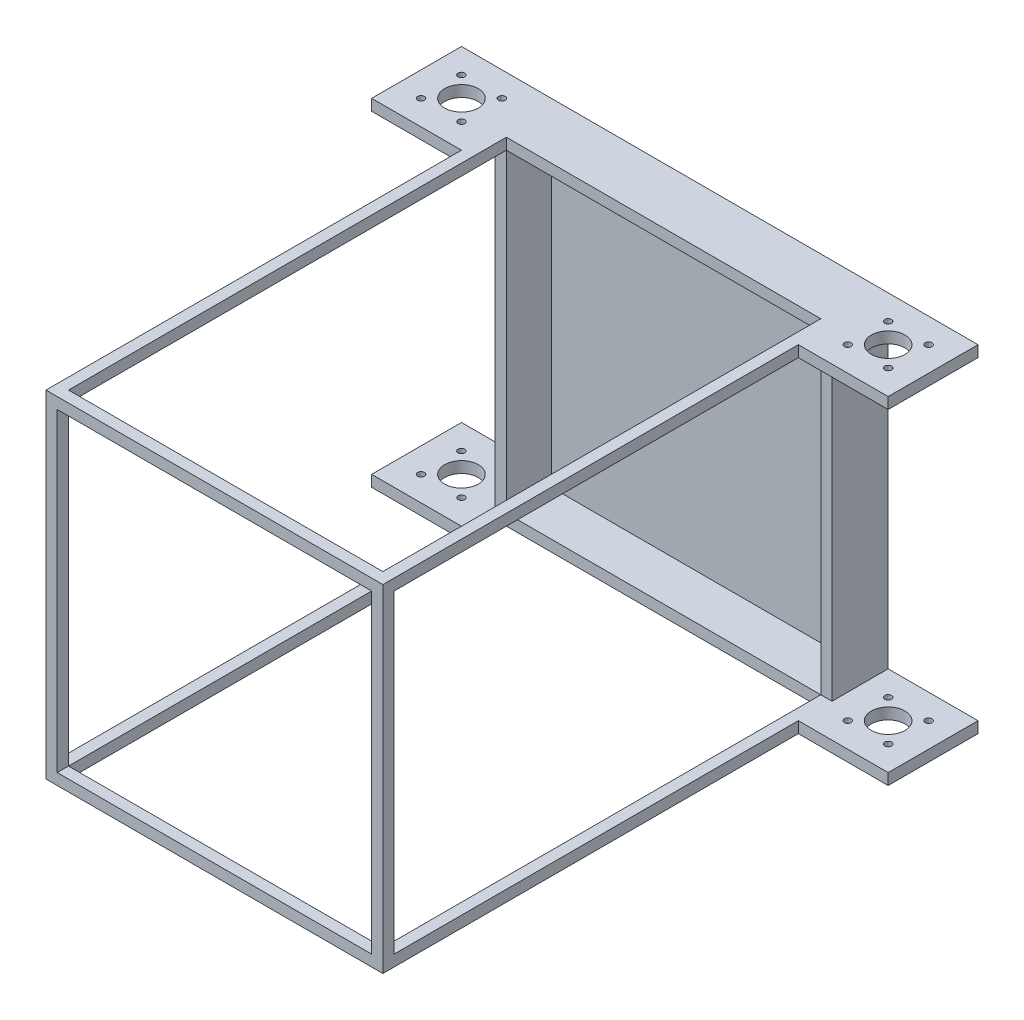
SolidWorks part; units mm, degrees
ref_plane "Спереди" through (0, 0, 0) normal (0, 0, 1) x (1, 0, 0)
ref_plane "Сверху" through (0, 0, 0) normal (0, 1, 0) x (1, 0, 0)
ref_plane "Справа" through (0, 0, 0) normal (1, 0, 0) x (0, 0, -1)
sketch "Эскиз1" plane through (0, 0, 0) normal (0, 0, 1) x (1, 0, 0)
  line L1 (5, 145) -> (145, 145)
  line L2 (5, 145) -> (5, 5)
  line L3 (5, 5) -> (145, 5)
  line L4 (145, 145) -> (145, 5)
  line L5 (0, 150) -> (150, 150)
  line L6 (0, 150) -> (0, 0)
  line L7 (0, 0) -> (150, 0)
  line L8 (150, 150) -> (150, 0)
  line L9 (150, 145) -> (190, 145)
  line L10 (150, 145) -> (150, 150)
  line L11 (150, 150) -> (190, 150)
  line L12 (190, 145) -> (190, 150)
  line L13 (0, 150) -> (-40, 150)
  line L14 (0, 150) -> (0, 145)
  line L15 (0, 145) -> (-40, 145)
  line L16 (-40, 150) -> (-40, 145)
  line L17 (150, 0) -> (190, 0)
  line L18 (150, 0) -> (150, 5)
  line L19 (150, 5) -> (190, 5)
  line L20 (190, 0) -> (190, 5)
  line L21 (0, 0) -> (-40, 0)
  line L22 (0, 0) -> (0, 5)
  line L23 (0, 5) -> (-40, 5)
  line L24 (-40, 0) -> (-40, 5)
  dimension "D1" = 150
  dimension "D2" = 150
  dimension "D3" = 5
  dimension "D4" = 5
  dimension "D5" = 5
  dimension "D6" = 5
  dimension "D7" = 5
  dimension "D8" = 40
  dimension "D9" = 40
  dimension "D10" = 5
  dimension "D11" = 40
  dimension "D12" = 5
  dimension "D13" = 40
  dimension "D14" = 5
extrude "Бобышка-Вытянуть2" add sketch "Эскиз1" along normal blind 5 contours L8 L5 L6 L7 L1 L4 L3 L2 region at (75, 147.8787, 0)
extrude "Бобышка-Вытянуть3" add sketch "Эскиз1<4>" along normal mid plane 40 contours L14 L15 L16 L13 | L22 L23 L24 L21 | L17 L20 L19 L18 | L11 L12 L9 L10
sketch "Эскиз1<4>" plane through (0, 0, 0) normal (0, 0, 1) x (1, 0, 0) same geometry as "Эскиз1"
sketch "Эскиз2" plane through (0, 0, 0) normal (0, -1, 0) x (1, 0, 0)
  line L0 (0, 20) -> (-40, 20) construction
  line L1 (-20, 20) -> (-20, -20) construction
  line L2 (0, -20) -> (-40, -20) construction
  line L4 (-29, -9) -> (-11, -9) construction
  line L5 (-29, -9) -> (-29, 9) construction
  line L6 (-29, 9) -> (-11, 9) construction
  line L7 (-11, -9) -> (-11, 9) construction
  line L8 (-29, -9) -> (-11, 9) construction
  line L9 (-29, 9) -> (-11, -9) construction
  circle A0 centre (-20, 0) radius 7.5
  circle A1 centre (-29, 9) radius 1.5
  circle A2 centre (-29, -9) radius 1.5
  circle A3 centre (-11, -9) radius 1.5
  circle A4 centre (-11, 9) radius 1.5
  dimension "D1" = 15
  dimension "D4" = 3
  dimension "D2" = 18
  dimension "D3" = 18
extrude "Вырез-Вытянуть1" cut sketch "Эскиз2" against normal through all
pattern_linear "Линейный массив1" count 2 spacing 190 along (1, 0, 0) of "Вырез-Вытянуть1"
sketch "Эскиз4" plane through (0, 0, 5) normal (0, 0, 1) x (1, 0, 0)
  line L1 (145, 5) -> (150, 5)
  line L2 (145, 5) -> (145, 0)
  line L3 (145, 0) -> (150, 0)
  line L4 (150, 5) -> (150, 0)
extrude "Бобышка-Вытянуть5" add sketch "Эскиз4" along normal blind 200
pattern_linear "Линейный массив2" count 2 spacing 145 along (0, 1, 0) count 2 spacing 145 along (-1, 0, 0) of "Бобышка-Вытянуть5"
pattern_linear "Линейный массив3" count 2 spacing 200 along (0, 0, 1) of "Бобышка-Вытянуть2"
sketch "Эскиз5" plane through (0, 0, 0) normal (0, 0, -1) x (-1, 0, 0)
  line L1 (-150, 150) -> (0, 150)
  line L2 (-150, 150) -> (-150, 0)
  line L3 (-150, 0) -> (0, 0)
  line L4 (0, 150) -> (0, 0)
extrude "Бобышка-Вытянуть6" add sketch "Эскиз5" along normal blind 20
sketch "Эскиз7" plane through (0, 0, 0) normal (0, 0, 1) x (1, 0, 0)
  line L0 (5, 145) -> (5, 5) construction
  line L1 (5, 5) -> (145, 5)
  line L2 (5, 5) -> (5, 145)
  line L3 (5, 145) -> (145, 145)
  line L4 (145, 5) -> (145, 145)
  line L5 (145, 145) -> (145, 5) construction
  line L8 (5, 145) -> (145, 145) construction
  dimension "D1" = 0
  dimension "D2" = 0
  dimension "D3" = 0
extrude "Вырез-Вытянуть3" cut sketch "Эскиз7" against normal blind 15
